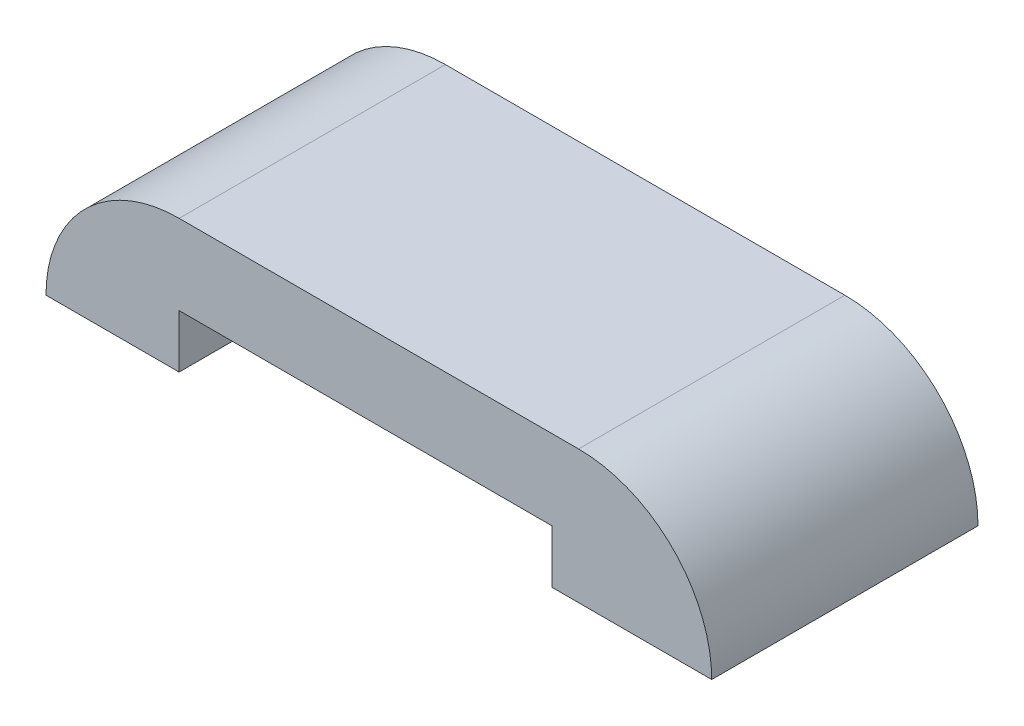
SolidWorks part; units mm, degrees
ref_plane "Front Plane" through (0, 0, 0) normal (0, 0, 1) x (1, 0, 0)
ref_plane "Top Plane" through (0, 0, 0) normal (0, 1, 0) x (1, 0, 0)
ref_plane "Right Plane" through (0, 0, 0) normal (1, 0, 0) x (0, 0, -1)
sketch "Sketch1" plane through (0, 0, 0) normal (0, 0, 1) x (1, 0, 0)
  line L0 (0, 0) -> (0, 5)
  line L1 (0, 5) -> (25, 5)
  line L2 (25, 5) -> (25, 0)
  line L3 (25, 0) -> (19, 0)
  line L4 (19, 0) -> (19, 2)
  line L5 (19, 2) -> (5, 2)
  line L6 (5, 2) -> (5, 0)
  line L7 (5, 0) -> (0, 0)
  dimension "D1" = 14
  dimension "D2" = 5
  dimension "D3" = 25
  dimension "D4" = 2
  dimension "D5" = 5
extrude "Boss-Extrude1" add sketch "Sketch1" along normal blind 10
fillet "Fillet2" radius 5 1 edges at (0, 5, 5) type face fillet first side face at (0, 2.5, 5) second side face at (12.5, 5, 5)
fillet "Fillet3" radius 5 1 edges at (25, 5, 5) type face fillet first side face at (25, 2.5, 5) second side face at (15, 5, 5)
